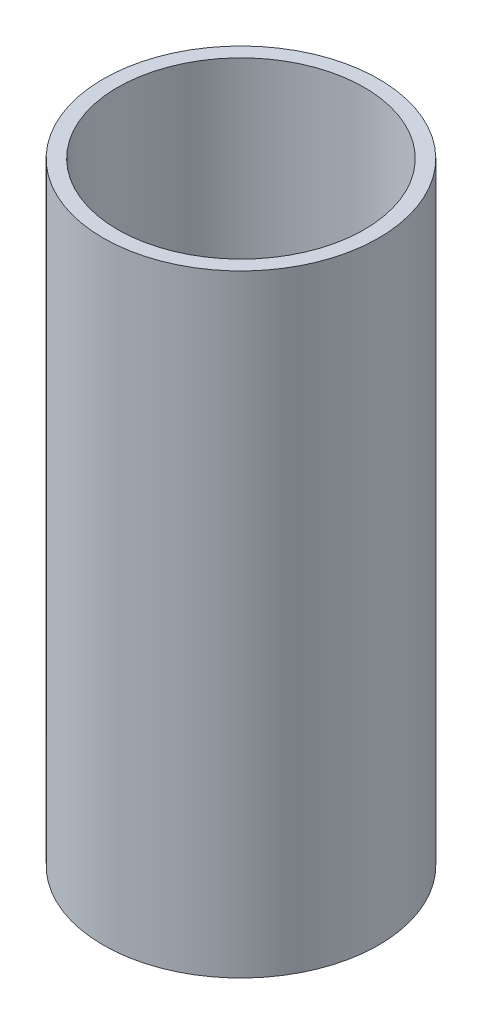
SolidWorks part; units mm, degrees
material "6061-T6 (SS)"
ref_plane "Front Plane" through (0, 0, 0) normal (0, 0, 1) x (1, 0, 0)
ref_plane "Top Plane" through (0, 0, 0) normal (0, 1, 0) x (1, 0, 0)
ref_plane "Right Plane" through (0, 0, 0) normal (1, 0, 0) x (0, 0, -1)
sketch "Sketch1" plane through (0, 0, 0) normal (0, 1, 0) x (1, 0, 0)
  circle A0 centre (0, 0) radius 57.15
  circle A1 centre (0, 0) radius 51.1302
  dimension "D1" = 114.3
  dimension "D2" = 102.2604
extrude "Boss-Extrude1" add sketch "Sketch1" along normal blind 254
